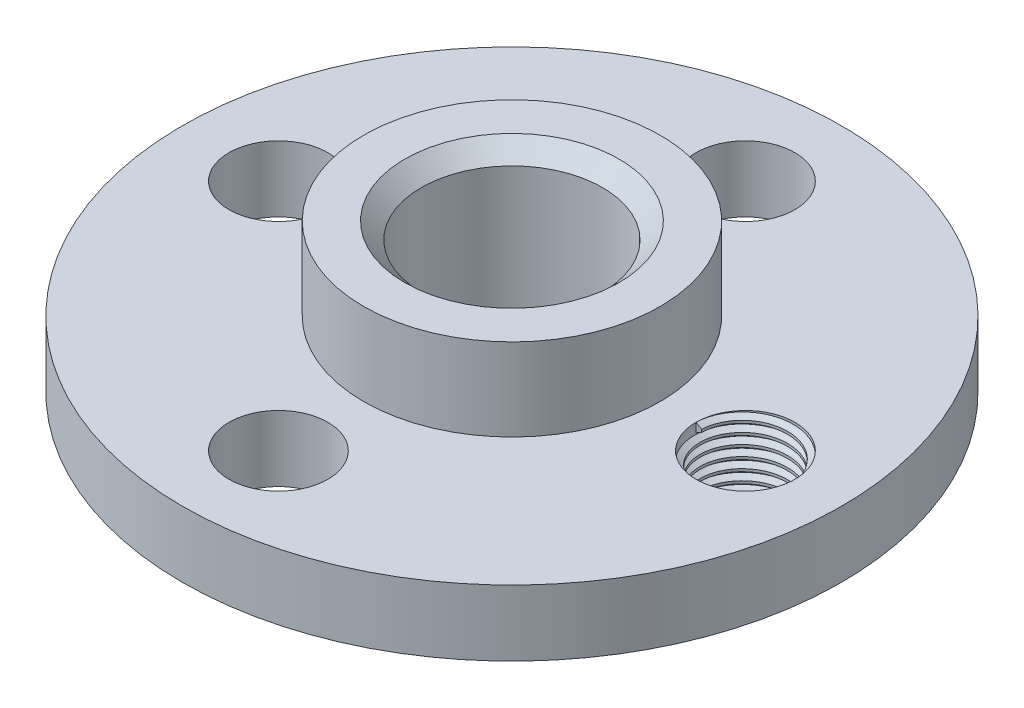
SolidWorks part; units mm, degrees
ref_plane "前视基准面" through (0, 0, 0) normal (0, 0, 1) x (1, 0, 0)
ref_plane "上视基准面" through (0, 0, 0) normal (0, 1, 0) x (1, 0, 0)
ref_plane "右视基准面" through (0, 0, 0) normal (1, 0, 0) x (0, 0, -1)
sketch "草图1" plane through (0, 0, 0) normal (0, 1, 0) x (1, 0, 0)
  circle A0 centre (0, 0) radius 10
  dimension "D1" = 20
extrude "凸台-拉伸1" add sketch "草图1" along normal blind 2
sketch "草图2" plane through (0, 2, 0) normal (0, 1, 0) x (1, 0, 0)
  circle A0 centre (0, 0) radius 4.5
  dimension "D1" = 9
extrude "凸台-拉伸2" add sketch "草图2" along normal blind 2.5
sketch "草图3" plane through (0, 2, 0) normal (0, 1, 0) x (1, 0, 0)
  line L0 (0, 0) -> (0, 3.7633) construction
  line L1 (0, 0) -> (3.1705, 0) construction
  circle A0 centre (7.0854, 0) radius 1.5
  circle A2 centre (0, -7.0854) radius 1.5
  circle A3 centre (-7.0854, 0) radius 1.5
  circle A4 centre (0, 7.0854) radius 1.5
  point P16 (0, 0)
  dimension "D1" = 3
  dimension "D2" = 4
extrude "切除-拉伸1" cut sketch "草图3" against normal blind 2.5
cosmetic thread "装饰螺纹线1" parameters "D2"=4
cosmetic thread "装饰螺纹线2" parameters "D2"=4
cosmetic thread "装饰螺纹线3" parameters "D2"=4
thread "螺纹线1" pitch 0.3175 method extrude profile "螺纹线轮廓1" start angle 0, offset 0, length 2, pitch 0.3175, diameter 3
ref_plane "基准面1" through (5.5854, 2, 0) normal (0, 0, 1) x (-1, 0, 0)
sketch "螺纹线轮廓1" plane through (5.5854, 2, 0) normal (0, 0, 1) x (-1, 0, 0)
  line L0 (0, 0) -> (0, 0.3175) construction
  line L11 (0, 0) -> (0, 0.2778)
  line L12 (0, 0.2778) -> (-0.1719, 0.1786)
  line L13 (-0.1719, 0.1786) -> (-0.1719, 0.0992)
  line L15 (-0.1719, 0.0992) -> (0, 0)
  line L17 (-0.1719, 0.1389) -> (0, 0.1389) construction
  point P2 (0, 0)
  dimension "Pitch" = 0.3175
  dimension "Profile_Angle" = 60
  dimension "Profile_Land" = 0.0794
  dimension "Profile_Height" = 0.1719
sketch "草图6" plane through (0, 4.5, 0) normal (0, 1, 0) x (1, 0, 0)
  circle A0 centre (0, 0) radius 2.75
  dimension "D1" = 5.5
extrude "切除-拉伸2" cut sketch "草图6" against normal blind 3.5
chamfer "倒角1" distance 0.5 angle 45 1 edges at (0, 4.5, 2.75)
sketch "草图7" plane through (0, 1, 0) normal (0, 1, 0) x (1, 0, 0)
  circle A1 centre (0, 0) radius 2.75
  circle A2 centre (0, 0) radius 2.75
  dimension "D1" = 0
extrude "切除-拉伸3" cut sketch "草图7" against normal blind 10
